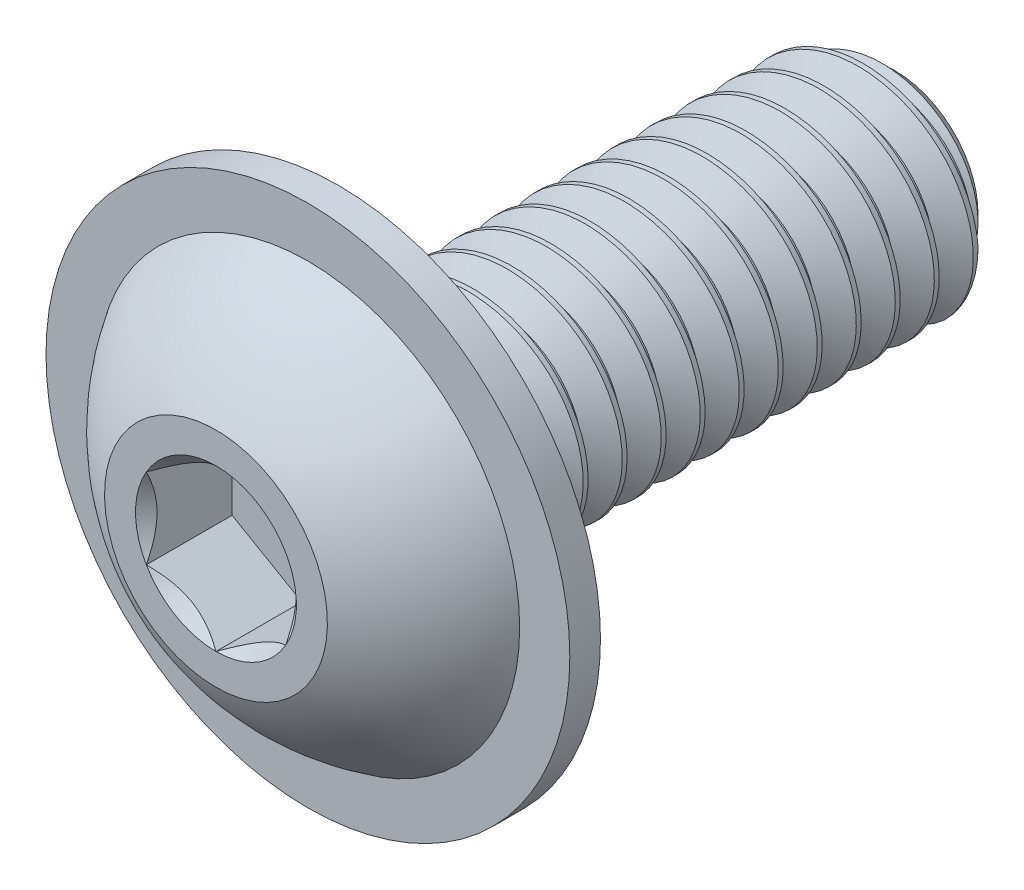
SolidWorks part; units mm, degrees
ref_plane "Front" through (0, 0, 0) normal (0, 0, 1) x (1, 0, 0)
ref_plane "Top" through (0, 0, 0) normal (0, 1, 0) x (1, 0, 0)
ref_plane "Right" through (0, 0, 0) normal (1, 0, 0) x (0, 0, -1)
sketch "Sketch1" plane through (0, 0, 0) normal (1, 0, 0) x (0, 0, -1)
  line L2 (2.2, 2) -> (12.2, 2)
  line L3 (12.2, 2) -> (12.2, 0)
  line L4 (12.2, 0) -> (2.2, 0)
  line L6 (1.65, 3.8) -> (2.2, 3.8) construction
  line L7 (12.2, 2) -> (12.2, -2) construction
  line L8 (0, 0) -> (2.2, 0) construction
  line L9 (2.2, 3.8) -> (2.2, -3.8) construction
  line L11 (2.2, 2) -> (2.2, 0)
  line L13 (0, 1.25) -> (0, -1.25) construction
  line L14 (0, 1.25) -> (0, 2) construction
  line L15 (1.65, 3.8) -> (1.65, 4.7) construction
  line L16 (1.65, 4.7) -> (2.2, 4.7) construction
  line L17 (2.2, 4.7) -> (2.2, 3.8) construction
  line L18 (2.2, 4.7) -> (2.2, -4.7) construction
  arc A3 (0, 2) -> (1.65, 3.8) centre (3.9886, 0) cw construction
  dimension "D1" = 0.55
  dimension "Head Ht" = 2.2
  dimension "Head Dia" = 7.6
  dimension "Dia" = 4
  dimension "Lg" = 10
  dimension "Hex" = 2.5
  dimension "Flange Dia" = 9.4
revolve "Revolve1" add sketch "Sketch1" angle 360 mid plane about L4
sketch "Sketch3" plane through (0, 0, -12.2) normal (0, 0, -1) x (-1, 0, 0)
  circle A0 centre (0, 0) radius 2
curve "Helix/Spiral1" pitch 0.7 height 10.7 radius 2 centre (0, 0, -12.2) axis (0, 0, 1) start towards (0, 1, 0)
sketch "Sketch2" plane through (0, 0, 0) normal (1, 0, 0) x (0, 0, -1)
  line L0 (12.2, 2) -> (12.8125, 2)
  line L1 (12.8125, 2) -> (12.55, 1.5453)
  line L2 (12.55, 1.5453) -> (12.4625, 1.5453)
  line L3 (12.4625, 1.5453) -> (12.2, 2)
  line L4 (12.3312, 1.7727) -> (12.6812, 1.7727) construction
  dimension "D1" = 60
  dimension "D2" = 0.0875
  dimension "D3" = 0.35
chamfer "Chamfer1" distance 0.525 angle 45 1 edges at (0, 2, -12.2)
sweep "Cut-Sweep1" cut profiles "Sketch2" path "Helix/Spiral1" align with end faces yes
sketch "Sketch7" plane through (0, 0, 0) normal (1, 0, 0) x (0, 0, -1)
  line L6 (1.65, 3.8) -> (2.2, 3.8) construction
  line L8 (0, 0) -> (2.2, 0) construction
  line L11 (2.2, 3.8) -> (2.2, -3.8) construction
  line L12 (1.65, 3.8) -> (2.2, 3.8)
  line L13 (0, 0) -> (2.2, 0)
  line L14 (0, 1.25) -> (0, -1.25) construction
  line L15 (2.2, 3.8) -> (2.2, 0)
  line L16 (0, 2) -> (0, 0)
  arc A2 (1.65, 3.8) -> (0, 2) centre (3.9886, 0) ccw construction
  arc A3 (1.65, 3.8) -> (0, 2) centre (3.9886, 0) ccw
revolve "Revolve2" add sketch "Sketch7" angle 360 mid plane about L13
sketch "Sketch11" plane through (0, 0, -2.2) normal (0, 0, -1) x (-1, 0, 0)
  circle A0 centre (0, 0) radius 4.7
extrude "Boss-Extrude3" add sketch "Sketch11" against normal up to vertex (0.55 mm away) up to point (0, 3.8, -1.65)
sketch "Sketch5" plane through (0, 0, 0) normal (0, 0, 1) x (1, 0, 0)
  line L1 (1.25, -0.7217) -> (1.25, 0.7217)
  line L2 (1.25, 0.7217) -> (0, 1.4434)
  line L3 (0, 1.4434) -> (-1.25, 0.7217)
  line L4 (-1.25, 0.7217) -> (-1.25, -0.7217)
  line L5 (-1.25, -0.7217) -> (0, -1.4434)
  line L6 (0, -1.4434) -> (1.25, -0.7217)
  circle A0 centre (0, 0) radius 1.25 construction
extrude "Cut-Extrude2" cut sketch "Sketch5" against normal blind 1.54
sketch "Sketch6" plane through (0, 0, 0) normal (0, 0, 1) x (1, 0, 0)
  circle A0 centre (0, 0) radius 1.4434
extrude "Cut-Extrude3" cut sketch "Sketch6" against normal blind 1.54 draft 45
sketch "Sketch9" [suppressed] plane through (0, 0, -5.0546) normal (0, 0, 1) x (1, 0, 0)
  circle A2 centre (0, 0) radius 4.7625
extrude "Boss-Extrude2" [suppressed] add sketch "Sketch9" against normal offset from surface (6.35 mm away) 31.75 up to face at (0, 1.475, -12.2)
sketch "Sketch10" plane through (0, 0, 0) normal (1, 0, 0) x (0, 0, -1)
  line L0 (12.2, 2) -> (12.2, -2) construction
  point P0 (11.15, -2)
  dimension "D1" = 1.05
equation "\"D3@Helix/Spiral1\" = \"Lg@Sketch1\" + \"D4@Helix/Spiral1\""
equation "\"D2@Sketch2\" = \"D4@Helix/Spiral1\" * .125"
equation "\"D3@Sketch2\" = \"D4@Helix/Spiral1\" * .5"
equation "\"D1@Chamfer1\" = \"D4@Helix/Spiral1\" * .75"
equation "\"D1@Cut-Extrude2\" = \"Head Ht@Sketch1\" * .7"
equation "\"D1@Sketch1\" = \"Head Ht@Sketch1\" * .25"
equation "\"D1@Sketch10\" = \"D4@Helix/Spiral1\" * 1.5"
equation "\"D1@Cut-Extrude3\" = \"D1@Cut-Extrude2\""
